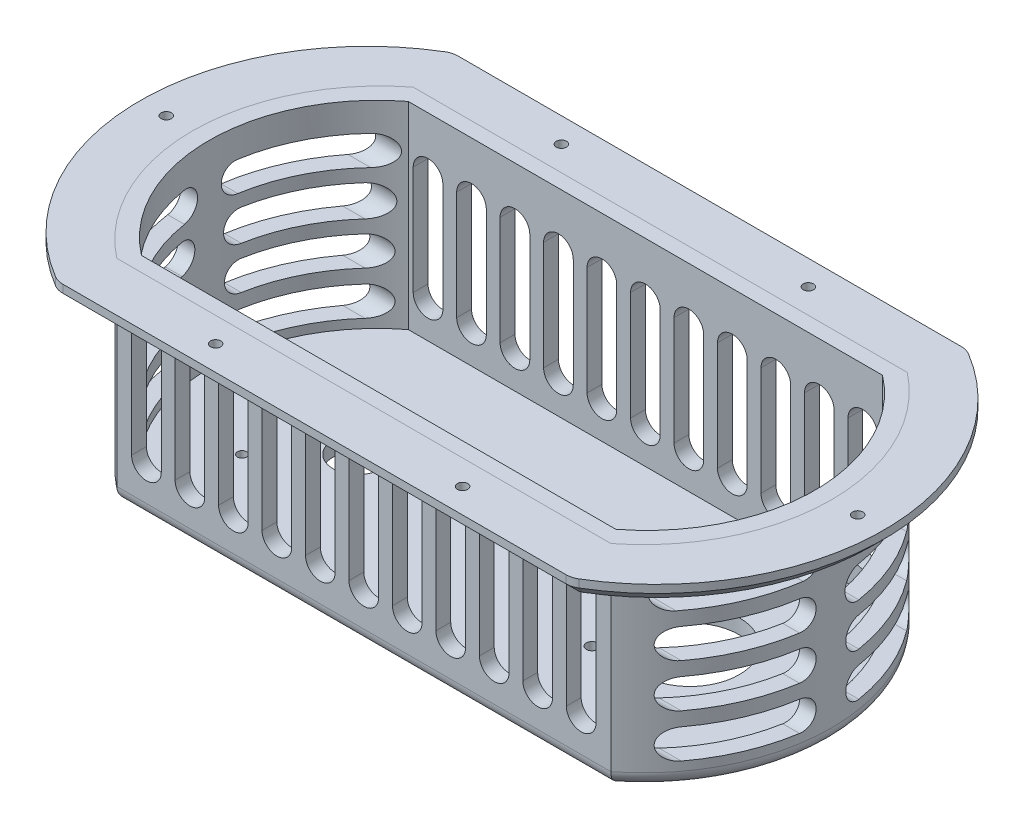
SolidWorks part; units mm, degrees
ref_plane "Front Plane" through (0, 0, 0) normal (0, 0, 1) x (1, 0, 0)
ref_plane "Top Plane" through (0, 0, 0) normal (0, 1, 0) x (1, 0, 0)
ref_plane "Right Plane" through (0, 0, 0) normal (1, 0, 0) x (0, 0, -1)
sketch "Sketch2" plane through (0, 0, 0) normal (0, 1, 0) x (1, 0, 0)
  line L0 (-130, 100) -> (130, 100)
  line L1 (125, 75) -> (-125, 75)
  line L3 (125, -75) -> (-125, -75)
  line L5 (125, 75) -> (-125, -75) construction
  line L6 (125, -75) -> (-125, 75) construction
  line L7 (-130, -100) -> (130, -100)
  line L8 (0, -124.0307) -> (0, 104.3694) construction
  arc A0 (-125, 75) -> (-125, -75) centre (-66.6905, 0) ccw
  arc A1 (125, 75) -> (125, -75) centre (66.6905, 0) cw
  arc A4 (-130, 100) -> (-130, -100) centre (-73.2109, 0) ccw
  arc A5 (130, 100) -> (130, -100) centre (73.2109, 0) cw
  point P0 (0, 0)
  point P14 (0, 100)
  dimension "D3" = 95
  dimension "D4" = 260
  dimension "D8" = 115
  dimension "D1" = 150
  dimension "D2" = 250
  dimension "D5" = 260
  dimension "D6" = 25
  dimension "D7" = 25
extrude "Boss-Extrude1" add sketch "Sketch2" along normal blind 10
sketch "Sketch3" plane through (0, 10, 0) normal (0, 1, 0) x (1, 0, 0)
  line L0 (-125, 75) -> (125, 75)
  line L1 (-125, -75) -> (125, -75)
  line L2 (-130, -100) -> (130, -100)
  line L3 (130, 100) -> (-130, 100)
  line L4 (-130, -100) -> (130, -100)
  line L5 (130, 100) -> (-130, 100)
  arc A1 (-125, 75) -> (-125, -75) centre (-66.6905, 0) ccw
  arc A2 (-130, 100) -> (-130, -100) centre (-73.2109, 0) ccw
  arc A3 (130, -100) -> (130, 100) centre (73.2109, 0) ccw
  arc A4 (-130, 100) -> (-130, -100) centre (-73.2109, 0) ccw
  arc A5 (130, -100) -> (130, 100) centre (73.2109, 0) ccw
  arc A6 (125, 75) -> (125, -75) centre (66.6905, 0) cw
  line M13 (125, -75) -> (-125, -75)
  arc M14 (-125, -75) -> (-125, 75) centre (-66.6905, 0) cw
  line M15 (-125, 75) -> (125, 75)
  arc M16 (125, 75) -> (125, -75) centre (66.6905, 0) cw
  dimension "D1" = 0
extrude "Boss-Extrude2" add sketch "Sketch3" against normal blind 100 separate body contours M13 M16 M15 M14 region at (0, 10, 0)
sketch "Sketch6" plane through (0, 10, 0) normal (0, 1, 0) x (-1, 0, 0)
  line L1 (120, 67.5) -> (-120, 67.5)
  line L3 (120, -67.5) -> (-120, -67.5)
  line L5 (120, 67.5) -> (-120, -67.5) construction
  line L6 (120, -67.5) -> (-120, 67.5) construction
  arc A0 (120, 67.5) -> (120, -67.5) centre (68.3401, 0) cw
  arc A1 (-120, 67.5) -> (-120, -67.5) centre (-68.3401, 0) ccw
  point P0 (0, 0)
  dimension "D3" = 85
  dimension "D1" = 240
  dimension "D2" = 135
extrude "Cut-Extrude1" cut sketch "Sketch6" against normal blind 85
fillet "Fillet2" radius 10 4 edges at (-130, 5, 100) (130, 5, 100) (-130, 5, -100) (130, 5, -100)
sketch "Sketch10" plane through (0, 0, 0) normal (0, -1, 0) x (1, 0, 0)
  line L0 (-125, 87.5) -> (125, 87.5) construction
  line L1 (-125, -87.5) -> (125, -87.5) construction
  line L2 (-127.2942, 100) -> (127.2942, 100) construction
  line L5 (125, -75) -> (-125, -75) construction
  line L6 (0, -31.9019) -> (0, -178.1053) construction
  line L7 (0, 118.6966) -> (0, 41.5647) construction
  line L8 (-125, 75) -> (125, 75) construction
  circle A0 centre (-174.9509, 0) radius 4.6
  circle A1 centre (174.9505, 0) radius 4.6
  circle A2 centre (-62.5, 87.5) radius 4.6
  circle A3 centre (62.5, 87.5) radius 4.6
  circle A4 centre (-62.5, -87.5) radius 4.6
  circle A5 centre (62.5, -87.5) radius 4.6
  arc A11 (-132.445, 98.5714) -> (-132.445, -98.5714) centre (-73.2109, 0) ccw construction
  arc A13 (125, -75) -> (125, 75) centre (66.6905, 0) ccw construction
  point P19 (-188.2109, 0)
  point P27 (161.6905, 0)
  point P31 (0, -87.5)
  point P32 (0, -75)
  point P35 (0, 87.5)
  point P38 (0, 75)
  dimension "D1" = 9.2
  dimension "D2" = 13.26
  dimension "D3" = 13.26
  dimension "D4" = 12.5
  dimension "D5" = 12.5
  dimension "D6" = 250
  dimension "D7" = 62.5
  dimension "D8" = 62.5
  dimension "D9" = 250
  dimension "D10" = 62.5
  dimension "D11" = 62.5
extrude "Cut-Extrude2" cut sketch "Sketch10" against normal blind 5 contours A0
extrude "Cut-Extrude3" cut sketch "Sketch10<3>" against normal blind 5 contours A4
sketch "Sketch10<3>" plane through (0, 0, 0) normal (0, -1, 0) x (1, 0, 0) same geometry as "Sketch10"
extrude "Cut-Extrude4" cut sketch "Sketch10<4>" against normal blind 5 contours A5
sketch "Sketch10<4>" plane through (0, 0, 0) normal (0, -1, 0) x (1, 0, 0) same geometry as "Sketch10"
extrude "Cut-Extrude5" cut sketch "Sketch10<5>" against normal blind 5 contours A1
sketch "Sketch10<5>" plane through (0, 0, 0) normal (0, -1, 0) x (1, 0, 0) same geometry as "Sketch10"
extrude "Cut-Extrude6" cut sketch "Sketch10<6>" against normal blind 5 contours A2
sketch "Sketch10<6>" plane through (0, 0, 0) normal (0, -1, 0) x (1, 0, 0) same geometry as "Sketch10"
extrude "Cut-Extrude7" cut sketch "Sketch10<7>" against normal blind 5 contours A3
sketch "Sketch10<7>" plane through (0, 0, 0) normal (0, -1, 0) x (1, 0, 0) same geometry as "Sketch10"
sketch "Sketch12" plane through (0, 5, 0) normal (0, -1, 0) x (1, 0, 0)
  circle A0 centre (-174.9509, 0) radius 2.6
  circle A1 centre (-62.5, 87.5) radius 2.6
  circle A2 centre (62.5, 87.5) radius 2.6
  circle A3 centre (174.9505, 0) radius 2.6
  circle A4 centre (62.5, -87.5) radius 2.6
  circle A5 centre (-62.5, -87.5) radius 2.6
  dimension "D1" = 5.2
extrude "Cut-Extrude8" cut sketch "Sketch12" against normal blind 5 contours A0
extrude "Cut-Extrude9" cut sketch "Sketch12<3>" against normal blind 5 contours A1
sketch "Sketch12<3>" plane through (0, 5, 0) normal (0, -1, 0) x (1, 0, 0) same geometry as "Sketch12"
extrude "Cut-Extrude10" cut sketch "Sketch12<4>" against normal blind 5 contours A2
sketch "Sketch12<4>" plane through (0, 5, 0) normal (0, -1, 0) x (1, 0, 0) same geometry as "Sketch12"
extrude "Cut-Extrude11" cut sketch "Sketch12<5>" against normal blind 5 contours A3
sketch "Sketch12<5>" plane through (0, 5, 0) normal (0, -1, 0) x (1, 0, 0) same geometry as "Sketch12"
extrude "Cut-Extrude12" cut sketch "Sketch12<6>" against normal blind 5 contours A5
sketch "Sketch12<6>" plane through (0, 5, 0) normal (0, -1, 0) x (1, 0, 0) same geometry as "Sketch12"
extrude "Cut-Extrude13" cut sketch "Sketch12<7>" against normal blind 5 contours A4
sketch "Sketch12<7>" plane through (0, 5, 0) normal (0, -1, 0) x (1, 0, 0) same geometry as "Sketch12"
sketch "Sketch35" plane through (0, -90, 0) normal (0, -1, 0) x (1, 0, 0)
  line L2 (125, 75) -> (-125, 75)
  line L3 (-125, -75) -> (125, -75)
  line L4 (125, 75) -> (-125, 75)
  line L5 (-125, -75) -> (125, -75)
  arc A2 (-125, 75) -> (-125, -75) centre (-66.6905, 0) ccw
  arc A3 (125, -75) -> (125, 75) centre (66.6905, 0) ccw
  arc A4 (-125, 75) -> (-125, -75) centre (-66.6905, 0) ccw
  arc A5 (125, -75) -> (125, 75) centre (66.6905, 0) ccw
  dimension "D1" = 0
extrude "Boss-Extrude3" add sketch "Sketch35" along normal blind 7.5
fillet "Fillet4" radius 7.5 4 edges at (0, -97.5, -75) (-161.6905, -97.5, 0) (0, -97.5, 75) (161.6905, -97.5, 0)
sketch "Sketch39" plane through (0, -75, 0) normal (0, 1, 0) x (1, 0, 0)
  line L2 (120, 67.5) -> (-120, 67.5)
  line L3 (-120, -67.5) -> (120, -67.5)
  line L4 (120, 67.5) -> (-120, 67.5)
  line L5 (-120, -67.5) -> (120, -67.5)
  arc A2 (120, -67.5) -> (120, 67.5) centre (68.3401, 0) ccw
  arc A3 (-120, 67.5) -> (-120, -67.5) centre (-68.3401, 0) ccw
  arc A4 (120, -67.5) -> (120, 67.5) centre (68.3401, 0) ccw
  arc A5 (-120, 67.5) -> (-120, -67.5) centre (-68.3401, 0) ccw
  dimension "D1" = 0
extrude "Cut-Extrude17" cut sketch "Sketch39" against normal blind 15
sketch "Sketch40" plane through (0, 0, -75) normal (0, 0, -1) x (-1, 0, 0)
  line L0 (0, 0) -> (0, -90) construction
  line L1 (-125, -90) -> (125, -90) construction
  line L2 (-125, -45) -> (125, -45) construction
  line L3 (-125, -90) -> (-125, 10) construction
  line L4 (125, -90) -> (125, 10) construction
  line L5 (0, -17.5) -> (0, -72.5) construction
  line L6 (7.5, -17.5) -> (7.5, -72.5)
  line L7 (-7.5, -17.5) -> (-7.5, -72.5)
  line L8 (14.5, -17.5) -> (14.5, -72.5)
  line L9 (29.5, -17.5) -> (29.5, -72.5)
  line L10 (22, -17.5) -> (22, -72.5) construction
  line L11 (36.5, -17.5) -> (36.5, -72.5)
  line L12 (51.5, -17.5) -> (51.5, -72.5)
  line L13 (44, -17.5) -> (44, -72.5) construction
  line L14 (58.5, -17.5) -> (58.5, -72.5)
  line L15 (73.5, -17.5) -> (73.5, -72.5)
  line L16 (66, -17.5) -> (66, -72.5) construction
  line L17 (80.5, -17.5) -> (80.5, -72.5)
  line L18 (95.5, -17.5) -> (95.5, -72.5)
  line L19 (88, -17.5) -> (88, -72.5) construction
  line L20 (102.5, -17.5) -> (102.5, -72.5)
  line L21 (117.5, -17.5) -> (117.5, -72.5)
  line L22 (110, -17.5) -> (110, -72.5) construction
  line L23 (-29.5, -17.5) -> (-29.5, -72.5)
  line L24 (-14.5, -17.5) -> (-14.5, -72.5)
  line L25 (-22, -17.5) -> (-22, -72.5) construction
  line L26 (-51.5, -17.5) -> (-51.5, -72.5)
  line L27 (-36.5, -17.5) -> (-36.5, -72.5)
  line L28 (-44, -17.5) -> (-44, -72.5) construction
  line L29 (-73.5, -17.5) -> (-73.5, -72.5)
  line L30 (-58.5, -17.5) -> (-58.5, -72.5)
  line L31 (-66, -17.5) -> (-66, -72.5) construction
  line L32 (-95.5, -17.5) -> (-95.5, -72.5)
  line L33 (-80.5, -17.5) -> (-80.5, -72.5)
  line L34 (-88, -17.5) -> (-88, -72.5) construction
  line L35 (-117.5, -17.5) -> (-117.5, -72.5)
  line L36 (-102.5, -17.5) -> (-102.5, -72.5)
  line L37 (-110, -17.5) -> (-110, -72.5) construction
  arc A0 (7.5, -17.5) -> (-7.5, -17.5) centre (0, -17.5) ccw
  arc A1 (-7.5, -72.5) -> (7.5, -72.5) centre (0, -72.5) ccw
  arc A2 (29.5, -17.5) -> (14.5, -17.5) centre (22, -17.5) ccw
  arc A3 (14.5, -72.5) -> (29.5, -72.5) centre (22, -72.5) ccw
  arc A4 (51.5, -17.5) -> (36.5, -17.5) centre (44, -17.5) ccw
  arc A5 (36.5, -72.5) -> (51.5, -72.5) centre (44, -72.5) ccw
  arc A6 (73.5, -17.5) -> (58.5, -17.5) centre (66, -17.5) ccw
  arc A7 (58.5, -72.5) -> (73.5, -72.5) centre (66, -72.5) ccw
  arc A8 (95.5, -17.5) -> (80.5, -17.5) centre (88, -17.5) ccw
  arc A9 (80.5, -72.5) -> (95.5, -72.5) centre (88, -72.5) ccw
  arc A10 (117.5, -17.5) -> (102.5, -17.5) centre (110, -17.5) ccw
  arc A11 (102.5, -72.5) -> (117.5, -72.5) centre (110, -72.5) ccw
  arc A12 (-14.5, -17.5) -> (-29.5, -17.5) centre (-22, -17.5) ccw
  arc A13 (-29.5, -72.5) -> (-14.5, -72.5) centre (-22, -72.5) ccw
  arc A14 (-36.5, -17.5) -> (-51.5, -17.5) centre (-44, -17.5) ccw
  arc A15 (-51.5, -72.5) -> (-36.5, -72.5) centre (-44, -72.5) ccw
  arc A16 (-58.5, -17.5) -> (-73.5, -17.5) centre (-66, -17.5) ccw
  arc A17 (-73.5, -72.5) -> (-58.5, -72.5) centre (-66, -72.5) ccw
  arc A18 (-80.5, -17.5) -> (-95.5, -17.5) centre (-88, -17.5) ccw
  arc A19 (-95.5, -72.5) -> (-80.5, -72.5) centre (-88, -72.5) ccw
  arc A20 (-102.5, -17.5) -> (-117.5, -17.5) centre (-110, -17.5) ccw
  arc A21 (-117.5, -72.5) -> (-102.5, -72.5) centre (-110, -72.5) ccw
  point P3 (0, -45)
  point P14 (0, -45)
  point P23 (22, -45)
  point P30 (44, -45)
  point P37 (66, -45)
  point P44 (88, -45)
  point P51 (110, -45)
  point P57 (-22, -45)
  point P64 (-44, -45)
  point P71 (-66, -45)
  point P78 (-88, -45)
  point P85 (-110, -45)
  dimension "D1" = 15
  dimension "D2" = 55
  dimension "D3" = 6
  dimension "D4" = 6
extrude "Cut-Extrude19" cut sketch "Sketch40" against normal through all
sketch "Sketch46" plane through (0, -97.5, 0) normal (0, -1, 0) x (1, 0, 0)
  line L0 (0, 0) -> (-144.535, 0) construction
  line L1 (-122.3681, 67.5) -> (-122.3681, -67.5) construction
  line L3 (-107.3681, 29.26) -> (-48.8481, 29.26) construction
  line L4 (-107.3681, 29.26) -> (-107.3681, -29.26) construction
  line L5 (-107.3681, -29.26) -> (-48.8481, -29.26) construction
  line L6 (-48.8481, 29.26) -> (-48.8481, -29.26) construction
  line L7 (-107.3681, 29.26) -> (-48.8481, -29.26) construction
  line L8 (-107.3681, -29.26) -> (-48.8481, 29.26) construction
  circle A0 centre (-107.3681, 29.26) radius 2.35
  circle A1 centre (-48.8481, 29.26) radius 2.35
  circle A2 centre (-48.8481, -29.26) radius 2.35
  circle A3 centre (-107.3681, -29.26) radius 2.35
  point P5 (-78.1081, 0)
  dimension "D4" = 4.7
  dimension "D1" = 58.52
  dimension "D2" = 58.52
  dimension "D3" = 15
extrude "Cut-Extrude20" cut sketch "Sketch46" against normal blind 10
sketch "Sketch48" plane through (0, 0, 0) normal (1, 0, 0) x (0, 0, -1)
  line L0 (0, 0) -> (0, -90) construction
  line L1 (-75, -90) -> (75, -90) construction
  line L2 (-75, -45) -> (75, -45) construction
  line L3 (-75, -90) -> (-75, 10) construction
  line L4 (75, -90) -> (75, 10) construction
  line L5 (-58.5, -12) -> (-13.5, -12) construction
  line L6 (-58.5, -4.5) -> (-13.5, -4.5)
  line L7 (-58.5, -19.5) -> (-13.5, -19.5)
  line L8 (13.5, -12) -> (58.5, -12) construction
  line L9 (13.5, -4.5) -> (58.5, -4.5)
  line L10 (13.5, -19.5) -> (58.5, -19.5)
  line L11 (-57, -34) -> (-15, -34) construction
  line L12 (-57, -26.5) -> (-15, -26.5)
  line L13 (-57, -41.5) -> (-15, -41.5)
  line L14 (15, -34) -> (57, -34) construction
  line L15 (15, -26.0734) -> (57, -26.0734)
  line L16 (15, -41.9266) -> (57, -41.9266)
  line L17 (-57, -56) -> (-15, -56) construction
  line L18 (-57, -48.5) -> (-15, -48.5)
  line L19 (-57, -63.5) -> (-15, -63.5)
  line L20 (15, -56) -> (57, -56) construction
  line L21 (15, -48.5) -> (57, -48.5)
  line L22 (15, -63.5) -> (57, -63.5)
  line L23 (-57, -78) -> (-15, -78) construction
  line L24 (-57, -70.5) -> (-15, -70.5)
  line L25 (-57, -85.5) -> (-15, -85.5)
  line L26 (15, -78) -> (57, -78) construction
  line L27 (15, -70.5) -> (57, -70.5)
  line L28 (15, -85.5) -> (57, -85.5)
  arc A0 (-58.5, -4.5) -> (-58.5, -19.5) centre (-58.5, -12) ccw
  arc A1 (-13.5, -19.5) -> (-13.5, -4.5) centre (-13.5, -12) ccw
  arc A2 (13.5, -4.5) -> (13.5, -19.5) centre (13.5, -12) ccw
  arc A3 (58.5, -19.5) -> (58.5, -4.5) centre (58.5, -12) ccw
  arc A4 (-57, -26.5) -> (-57, -41.5) centre (-57, -34) ccw
  arc A5 (-15, -41.5) -> (-15, -26.5) centre (-15, -34) ccw
  arc A6 (15, -26.0734) -> (15, -41.9266) centre (15, -34) ccw
  arc A7 (57, -41.9266) -> (57, -26.0734) centre (57, -34) ccw
  arc A8 (-57, -48.5) -> (-57, -63.5) centre (-57, -56) ccw
  arc A9 (-15, -63.5) -> (-15, -48.5) centre (-15, -56) ccw
  arc A10 (15, -48.5) -> (15, -63.5) centre (15, -56) ccw
  arc A11 (57, -63.5) -> (57, -48.5) centre (57, -56) ccw
  arc A12 (-57, -70.5) -> (-57, -85.5) centre (-57, -78) ccw
  arc A13 (-15, -85.5) -> (-15, -70.5) centre (-15, -78) ccw
  arc A14 (15, -70.5) -> (15, -85.5) centre (15, -78) ccw
  arc A15 (57, -85.5) -> (57, -70.5) centre (57, -78) ccw
  point P13 (-36, -12)
  point P18 (36, -12)
  point P25 (0, -45)
  point P28 (-36, -34)
  point P33 (36, -34)
  point P42 (-36, -56)
  point P47 (36, -56)
  point P54 (-36, -78)
  point P61 (36, -78)
  dimension "D1" = 45
  dimension "D2" = 39
  dimension "D3" = 15
  dimension "D4" = 15
  dimension "D5" = 39
  dimension "D6" = 15
  dimension "D7" = 15
  dimension "D8" = 7
  dimension "D9" = 7
  dimension "D10" = 7
  dimension "D11" = 4.5
extrude "Cut-Extrude21" cut sketch "Sketch48" against normal mid plane 330
chamfer "Chamfer1" distance 6 angle 45 8 edges at (188.2109, 0, 0) (129.9668, 0, -99.6362) (129.9668, 0, 99.6362) (0, 0, -100) (0, 0, 100) (-129.9668, 0, -99.6362) (-129.9668, 0, 99.6362) (-188.2109, 0, 0)
sketch "Sketch49" plane through (0, -97.5, 0) normal (0, -1, 0) x (-1, 0, 0)
  line L0 (-65.2513, -24.7487) -> (-90, 0) construction
  line L1 (0, 0) -> (-90, 0) construction
  circle A0 centre (-90, 0) radius 25
  circle A1 centre (-65.2513, -24.7487) radius 2.9
  circle A2 centre (-114.7487, -24.7487) radius 2.9
  circle A3 centre (-114.7487, 24.7487) radius 2.9
  circle A4 centre (-65.2513, 24.7487) radius 2.9
  point P15 (-90, 0)
  dimension "D1" = 50
  dimension "D4" = 5.8
  dimension "D2" = 90
  dimension "D3" = 45
  dimension "D5" = 35
  dimension "D6" = 4
extrude "Cut-Extrude22" cut sketch "Sketch49" against normal through all
sketch "Sketch50" plane through (0, -97.5, 0) normal (0, -1, 0) x (1, 0, 0)
  line L0 (-107.3681, 29.26) -> (-48.8481, -29.26) construction
  line L1 (-48.8481, 29.26) -> (-107.3681, -29.26) construction
  circle A0 centre (-78.1081, 0) radius 12.5
  dimension "D1" = 25
extrude "Cut-Extrude23" cut sketch "Sketch50" against normal through all both
